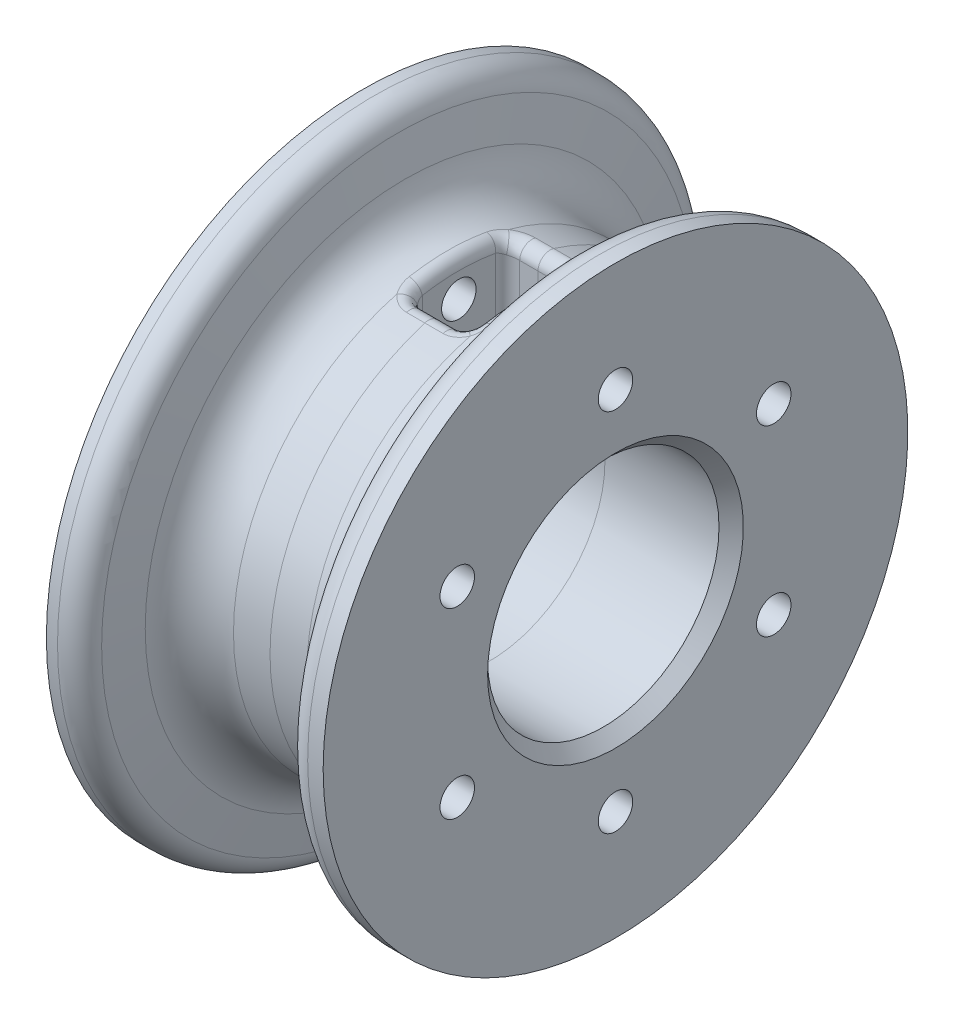
SolidWorks part; units mm, degrees
ref_plane "Front" through (0, 0, 0) normal (0, 0, 1) x (1, 0, 0)
ref_plane "Top" through (0, 0, 0) normal (0, 1, 0) x (1, 0, 0)
ref_plane "Right" through (0, 0, 0) normal (1, 0, 0) x (0, 0, -1)
ref_axis "Axis1" through (80.9, 0, 0) along (-1, 0, 0)
sketch "Sketch1" plane through (0, 0, 0) normal (0, 1, 0) x (1, 0, 0)
  line L0 (0, 16.6687) -> (0, 41.275)
  line L1 (0, 41.275) -> (1.4537, 41.275)
  line L2 (4.5805, 38.6513) -> (5.432, 33.8223)
  line L3 (11.6855, 28.575) -> (21.2105, 28.575)
  line L4 (27.4641, 33.8223) -> (27.7557, 35.4763)
  line L5 (30.8825, 38.1) -> (32.8961, 38.1)
  line L6 (32.8961, 38.1) -> (32.8961, 16.6688)
  line L8 (1.5875, 15.0812) -> (31.3086, 15.0812)
  line L9 (0, 0) -> (32.8961, 0) construction
  line L10 (16.448, 28.575) -> (16.448, 0) construction
  line L11 (32.8961, 0) -> (32.8961, -15.5649) construction
  line L12 (32.8961, 16.6688) -> (31.3086, 15.0812)
  line L13 (0, 16.6687) -> (1.5875, 15.0812)
  arc A0 (21.2105, 28.575) -> (27.4641, 33.8223) centre (21.2105, 34.925) ccw
  arc A1 (5.432, 33.8223) -> (11.6855, 28.575) centre (11.6855, 34.925) ccw
  arc A2 (27.7557, 35.4763) -> (30.8825, 38.1) centre (30.8825, 34.925) cw
  arc A3 (1.4537, 41.275) -> (4.5805, 38.6513) centre (1.4537, 38.1) cw
  point P0 (32.8961, 15.0813)
  point P11 (0, 15.0812)
  point P24 (4.1179, 41.275)
  dimension "D6" = 6.35
  dimension "D7" = 3.175
  dimension "D1" = 30.1625
  dimension "D2" = 80
  dimension "D3" = 12.7
  dimension "D4" = 57.15
  dimension "D5" = 80
  dimension "D8" = 9.525
  dimension "D9" = 9.525
revolve "Revolve1" add sketch "Sketch1" angle 360 about L9
hole_wizard "#8 Clearance Hole1" positions "Sketch2" profile "Sketch3" hole size "#8" standard "ANSI Inch" end condition through all
sketch "Sketch2" plane through (0, 0, 0) normal (-1, 0, 0) x (0, 0, 1)
  circle A0 centre (-20.6222, -11.9062) radius 2.15 construction
  circle A1 centre (0, -23.8125) radius 2.15 construction
  circle A2 centre (20.6222, -11.9063) radius 2.15 construction
  circle A3 centre (20.6222, 11.9062) radius 2.15 construction
  circle A4 centre (-20.6222, 11.9063) radius 2.15 construction
  circle A5 centre (0, 23.8125) radius 2.15 construction
  point P0 (0, -23.8125)
  point P2 (20.6222, -11.9063)
  point P4 (20.6222, 11.9062)
  point P6 (-20.6222, -11.9062)
  point P8 (-20.6222, 11.9063)
  point P26 (0, 23.8125)
sketch "Sketch3" plane through (0, -23.8125, 0) normal (0, 1, 0) x (0, 0, 1)
  line L0 (0, 0) -> (0, 32.8961)
  line L1 (0, 32.8961) -> (2.2479, 32.8961)
  line L2 (2.2479, 32.8961) -> (2.2479, 0)
  line L5 (2.2479, 0) -> (0, 0)
  line L11 (0, -6.35) -> (0, 107.95) construction
  dimension "Thru Hole Dia." = 4.4958
  dimension "Thru Hole Depth" = 32.8961
sketch "Sketch4" plane through (0, 0, 0) normal (0, 1, 0) x (1, 0, 0)
  line L0 (16.448, 28.575) -> (16.448, 0) construction
  line L1 (12.4793, 6.35) -> (20.4168, 6.35)
  line L2 (12.4793, 6.35) -> (12.4793, -6.35)
  line L3 (12.4793, -6.35) -> (20.4168, -6.35)
  line L4 (20.4168, 6.35) -> (20.4168, -6.35)
  point P4 (12.4793, 0)
  point P8 (16.448, 6.35)
  dimension "D1" = 7.9375
  dimension "D2" = 12.7
extrude "Cut-Extrude1" cut sketch "Sketch4" along normal blind 64.262
fillet "Fillet1" radius 1.5875 4 edges at (12.4793, 20.7699, -6.35) (20.4168, 20.7699, -6.35) (20.4168, 20.7699, 6.35) (12.4793, 20.7699, 6.35)
fillet "Fillet2" radius 1.5875 16 edges at (16.448, 27.8605, 6.35) (20.0587, 27.987, 5.7668) (20.4168, 28.575, 0) (19.8036, 27.9346, -6.0159) (16.448, 27.8605, -6.35) (12.8373, 27.987, -5.7668) (12.4793, 28.575, 0) (13.0925, 27.9346, 6.0159) (16.448, 13.6792, 6.35) (12.8672, 13.9204, 5.8023) (12.4793, 15.0812, 0) (13.1394, 13.8141, -6.051) (16.448, 13.6792, -6.35) (20.0289, 13.9204, -5.8023) (20.4168, 15.0812, 0) (19.7566, 13.8141, 6.051)
ref_plane "Plane1" through (16.448, 0, 0) normal (1, 0, 0) x (0, 0, -1)
split "Split1" trim tools "Plane1" bodies to split 105 resulting bodies 106 107
